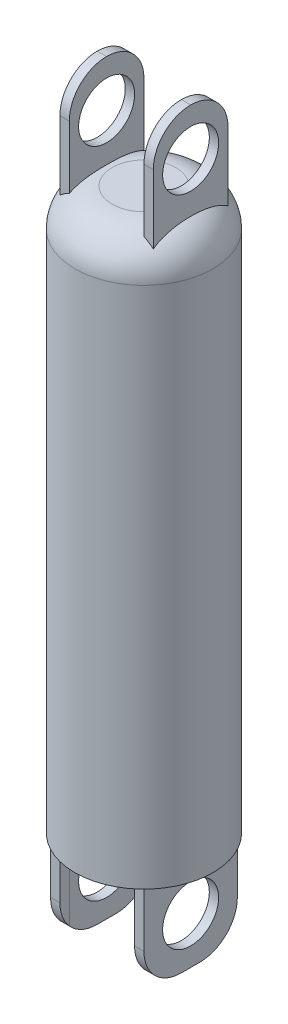
SolidWorks part; units mm, degrees
ref_plane "Front Plane" through (0, 0, 0) normal (0, 0, 1) x (1, 0, 0)
ref_plane "Top Plane" through (0, 0, 0) normal (0, 1, 0) x (1, 0, 0)
ref_plane "Right Plane" through (0, 0, 0) normal (1, 0, 0) x (0, 0, -1)
sketch "Sketch1" plane through (0, 0, 0) normal (0, 1, 0) x (1, 0, 0)
  circle A0 centre (0, 0) radius 3.7
extrude "Boss-Extrude1" add sketch "Sketch1" along normal blind 30
sketch "Sketch2" plane through (0, 30, 0) normal (0, 1, 0) x (1, 0, 0)
  line L1 (2.5, 2) -> (-2.5, 2)
  line L2 (2.5, 2) -> (2.5, -2)
  line L3 (2.5, -2) -> (-2.5, -2)
  line L4 (-2.5, 2) -> (-2.5, -2)
  line L5 (2.5, 2) -> (-2.5, -2) construction
  line L6 (2.5, -2) -> (-2.5, 2) construction
  line L10 (-2, 1.5) -> (-2, -1.5)
  line L11 (2, -1.5) -> (-2, -1.5)
  line L12 (2, 1.5) -> (2, -1.5)
  line L13 (2, 1.5) -> (-2, 1.5)
  point P0 (0, 0)
  dimension "D1" = 5
  dimension "D2" = 4
  dimension "D3" = 0.5
extrude "Boss-Extrude2" add sketch "Sketch2" along normal blind 5
sketch "Sketch3" plane through (0, 35, 0) normal (0, 1, 0) x (1, 0, 0)
  line L1 (2, 2.2661) -> (-2, 2.2661)
  line L2 (2, 2.2661) -> (2, -2.2661)
  line L3 (2, -2.2661) -> (-2, -2.2661)
  line L4 (-2, 2.2661) -> (-2, -2.2661)
  line L5 (2, 2.2661) -> (-2, -2.2661) construction
  line L6 (2, -2.2661) -> (-2, 2.2661) construction
  point P0 (0, 0)
extrude "Cut-Extrude1" cut sketch "Sketch3" against normal blind 5
sketch "Sketch4" plane through (-2.5, 0, 0) normal (-1, 0, 0) x (0, 0, 1)
  line L0 (0, 35) -> (0, 32.5)
  line L1 (-2, 35) -> (2, 35) construction
  circle A0 centre (0, 32.5) radius 1.5
extrude "Cut-Extrude2" cut sketch "Sketch4" against normal blind 15 contours A0 region at (-2.5, 31.4693, -1.0307)
fillet "Fillet1" radius 2 4 edges at (-2.25, 35, 2) (-2.25, 35, -2) (2.25, 35, -2) (2.25, 35, 2)
fillet "Fillet2" radius 2 1 edges at (0, 30, 3.7)
sketch "Sketch5" plane through (0, 0, 0) normal (0, -1, 0) x (1, 0, 0)
  line L0 (-2, 2) -> (-2, -2)
  line L1 (2.5, 2.5) -> (-2.5, 2.5)
  line L2 (2.5, 2.5) -> (2.5, -2.5)
  line L3 (2.5, -2.5) -> (-2.5, -2.5)
  line L4 (-2.5, 2.5) -> (-2.5, -2.5)
  line L5 (2.5, 2.5) -> (-2.5, -2.5) construction
  line L6 (2.5, -2.5) -> (-2.5, 2.5) construction
  line L7 (2, -2) -> (-2, -2)
  line L8 (2, 2) -> (2, -2)
  line L9 (2, 2) -> (-2, 2)
  point P0 (0, 0)
  dimension "D1" = 5
  dimension "D2" = 5
  dimension "D3" = 0.5
extrude "Boss-Extrude3" add sketch "Sketch5" along normal blind 5
sketch "Sketch6" plane through (0, -5, 0) normal (0, -1, 0) x (1, 0, 0)
  line L1 (1.9973, 2.9093) -> (-1.9973, 2.9093)
  line L2 (1.9973, 2.9093) -> (1.9973, -2.9093)
  line L3 (1.9973, -2.9093) -> (-1.9973, -2.9093)
  line L4 (-1.9973, 2.9093) -> (-1.9973, -2.9093)
  line L5 (1.9973, 2.9093) -> (-1.9973, -2.9093) construction
  line L6 (1.9973, -2.9093) -> (-1.9973, 2.9093) construction
  point P0 (0, 0)
extrude "Cut-Extrude3" cut sketch "Sketch6" against normal blind 5
sketch "Sketch7" plane through (2.5, 0, 0) normal (1, 0, 0) x (0, 0, -1)
  line L0 (0, -5) -> (0, -2.5)
  line L1 (2.5, -5) -> (-2.5, -5) construction
  circle A0 centre (0, -2.5) radius 1.5
extrude "Cut-Extrude4" cut sketch "Sketch7" against normal blind 5 contours A0 region at (2.5, -3.5307, -1.0307)
fillet "Fillet3" radius 2 4 edges at (-2.2487, -5, -2.5) (-2.2487, -5, 2.5) (2.2487, -5, 2.5) (2.2487, -5, -2.5)
